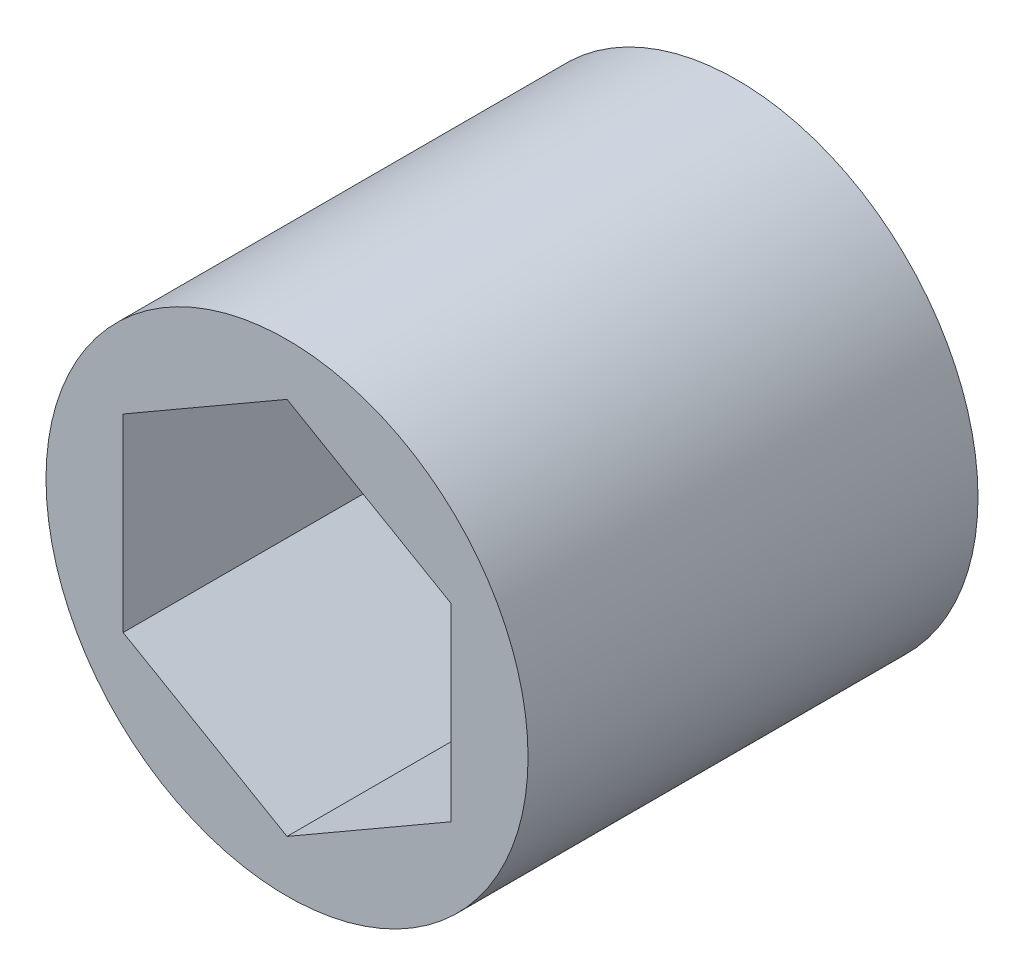
SolidWorks part; units mm, degrees
material "PET"
ref_plane "Front Plane" through (0, 0, 0) normal (0, 0, 1) x (1, 0, 0)
ref_plane "Top Plane" through (0, 0, 0) normal (0, 1, 0) x (1, 0, 0)
ref_plane "Right Plane" through (0, 0, 0) normal (1, 0, 0) x (0, 0, -1)
sketch "Sketch1" plane through (0, 0, 0) normal (0, 0, 1) x (1, 0, 0)
  line L1 (0, 7.479) -> (-6.477, 3.7395)
  line L2 (-6.477, 3.7395) -> (-6.477, -3.7395)
  line L3 (-6.477, -3.7395) -> (0, -7.479)
  line L4 (0, -7.479) -> (6.477, -3.7395)
  line L5 (6.477, -3.7395) -> (6.477, 3.7395)
  line L6 (6.477, 3.7395) -> (0, 7.479)
  circle A0 centre (0, 0) radius 9.525
  circle A1 centre (0, 0) radius 6.477 construction
  dimension "D1" = 19.05
  dimension "D2" = 12.954
extrude "Boss-Extrude1" add sketch "Sketch1" along normal mid plane 17.78
